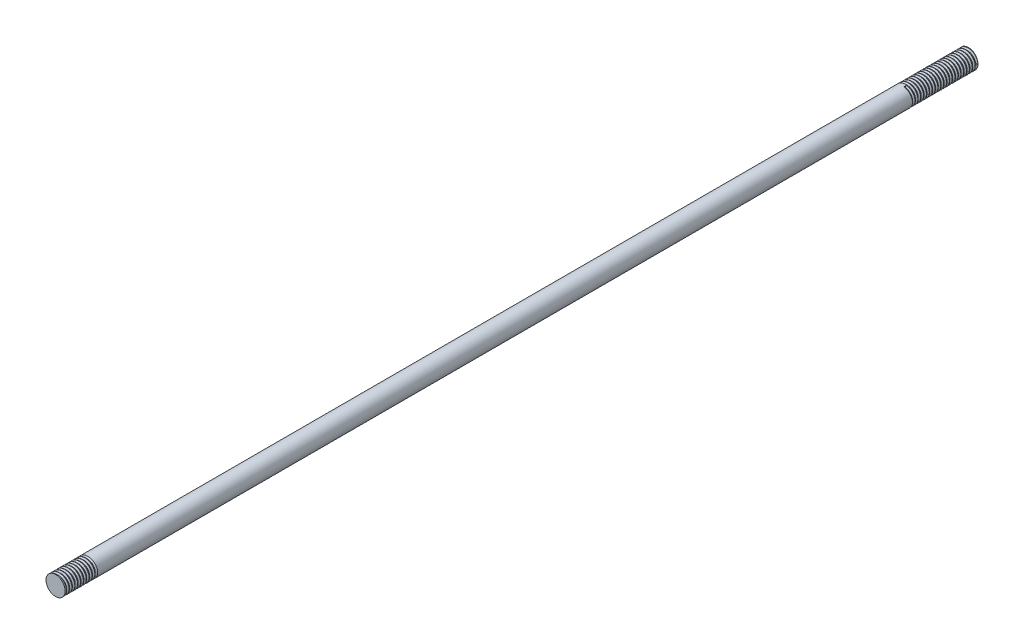
SolidWorks part; units mm, degrees
ref_plane "Alzado" through (0, 0, 0) normal (0, 0, 1) x (1, 0, 0)
ref_plane "Planta" through (0, 0, 0) normal (0, 1, 0) x (1, 0, 0)
ref_plane "Vista lateral" through (0, 0, 0) normal (1, 0, 0) x (0, 0, -1)
sketch "Croquis1" plane through (0, 0, 0) normal (0, 0, 1) x (1, 0, 0)
  circle A0 centre (0, 0) radius 1.5
  dimension "D1" = 3
extrude "Saliente-Extruir1" add sketch "Croquis1" along normal blind 143.36
cosmetic thread "Rosca cosmética1"
thread "Rosca1" pitch 0.45 method cut profile "Perfil de rosca1" start angle 0, offset 0, length 5, pitch 0.45, diameter 3
ref_plane "Plano1" through (-1.5, 0, 143.36) normal (0, -1, 0) x (-1, 0, 0)
sketch "Perfil de rosca1" plane through (-1.5, 0, 143.36) normal (0, -1, 0) x (-1, 0, 0)
  line L0 (0, 0) -> (0, 0.45) construction
  line L11 (0, 0) -> (0, 0.3937)
  line L12 (0, 0.3937) -> (-0.2436, 0.2531)
  line L13 (-0.2436, 0.2531) -> (-0.2436, 0.1406)
  line L15 (-0.2436, 0.1406) -> (0, 0)
  line L17 (-0.2436, 0.1969) -> (0, 0.1969) construction
  point P2 (0, 0)
  dimension "Pitch" = 0.45
  dimension "Profile_Angle" = 60
  dimension "Profile_Land" = 0.1125
  dimension "Profile_Height" = 0.2436
thread "Rosca2" pitch 0.45 method cut profile "Perfil de rosca2" start angle 0, offset 0, length 10, pitch 0.45, diameter 3
ref_plane "Plano2" through (1.5, 0, 0) normal (0, -1, 0) x (1, 0, 0)
sketch "Perfil de rosca2" plane through (1.5, 0, 0) normal (0, -1, 0) x (1, 0, 0)
  line L0 (0, 0) -> (0, 0.45) construction
  line L11 (0, 0) -> (0, 0.3937)
  line L12 (0, 0.3937) -> (-0.2436, 0.2531)
  line L13 (-0.2436, 0.2531) -> (-0.2436, 0.1406)
  line L15 (-0.2436, 0.1406) -> (0, 0)
  line L17 (-0.2436, 0.1969) -> (0, 0.1969) construction
  point P2 (0, 0)
  dimension "Pitch" = 0.45
  dimension "Profile_Angle" = 60
  dimension "Profile_Land" = 0.1125
  dimension "Profile_Height" = 0.2436
equation "\"D1@Saliente-Extruir1\"=132,8367"
